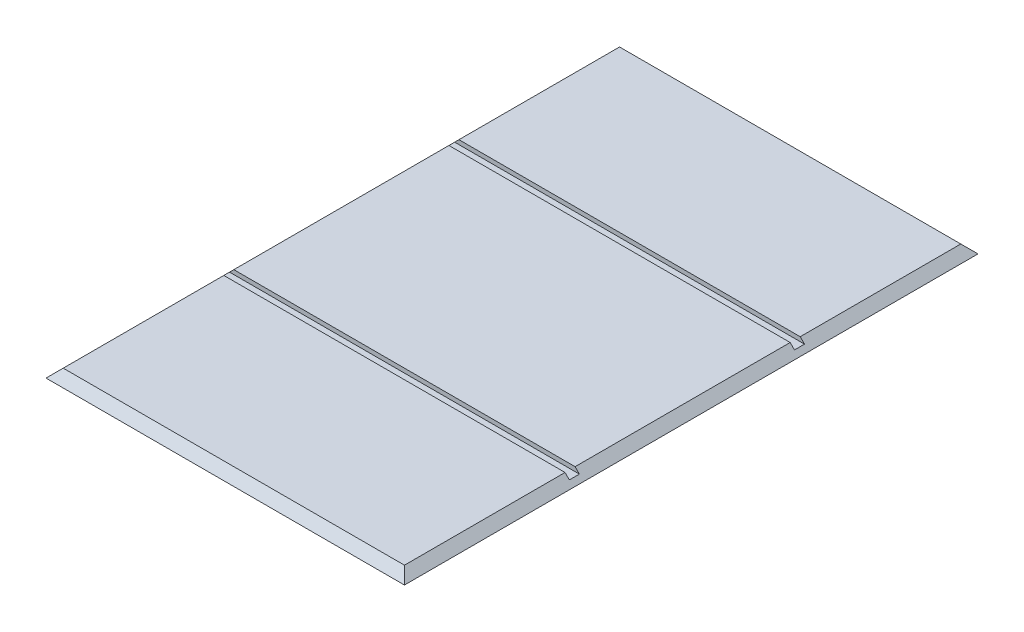
SolidWorks part; units mm, degrees
other "Markup1"
sketch "Sketch4" plane through (0, 750, 0) normal (-0.3936, 0.2648, -0.8803) x (-0.8349, 0.2978, 0.4628)
ref_plane "Front Plane" through (0, 0, 0) normal (0, 0, 1) x (1, 0, 0)
ref_plane "Top Plane" through (0, 0, 0) normal (0, 1, 0) x (1, 0, 0)
ref_plane "Right Plane" through (0, 0, 0) normal (1, 0, 0) x (0, 0, -1)
sketch "Sketch5" plane through (0, 0, 0) normal (0, 1, 0) x (1, 0, 0)
  line L1 (0, 0) -> (500, 0)
  line L2 (0, 0) -> (0, 800)
  line L3 (0, 800) -> (500, 800)
  line L4 (500, 0) -> (500, 800)
  line L5 (0, 250) -> (500, 250)
  line L6 (0, 250) -> (0, 236)
  line L7 (0, 236) -> (500, 236)
  line L8 (500, 250) -> (500, 236)
  line L9 (0, 564) -> (500, 564)
  line L10 (0, 564) -> (0, 550)
  line L11 (0, 550) -> (500, 550)
  line L12 (500, 564) -> (500, 550)
  line L13 (0, 0) -> (500, 0)
  line L14 (0, 0) -> (0, 12)
  line L15 (0, 12) -> (500, 12)
  line L16 (500, 0) -> (500, 12)
  line L17 (0, 800) -> (500, 800)
  line L18 (0, 800) -> (0, 788)
  line L19 (0, 788) -> (500, 788)
  line L20 (500, 800) -> (500, 788)
  dimension "D1" = 800
  dimension "D2" = 500
  dimension "D3" = 14
  dimension "D4" = 14
  dimension "D5" = 300
  dimension "D6" = 224
  dimension "D7" = 12
  dimension "D8" = 12
  dimension "D9" = 224
extrude "Boss-Extrude1" add sketch "Sketch5" along normal blind 12 contours L11 L2 L5 L4 | L2 L15 L4 L7 | L19 L2 L9 L4 region at (250, 0, -124) region at (250, 0, -400) region at (250, 0, -676)
extrude "Boss-Extrude2" add sketch "Sketch5<3>" along normal blind 6 contours L2 L7 L4 L5 | L2 L11 L4 L9 region at (250, 0, -243) region at (250, 0, -557)
sketch "Sketch5<3>" plane through (0, 0, 0) normal (0, 1, 0) x (1, 0, 0) same geometry as "Sketch5"
extrude "Boss-Extrude3" add sketch "Sketch5<4>" along normal blind 12 contours L15 L2 L1 L4 | L2 L19 L4 L3 region at (250, 0, -6) region at (250, 0, -794)
sketch "Sketch5<4>" plane through (0, 0, 0) normal (0, 1, 0) x (1, 0, 0) same geometry as "Sketch5"
chamfer "Chamfer1" distance 12 distance2 12 4 edges at (250, 12, 0) (250, 12, -800) (0, 12, -118) (500, 12, -118)
